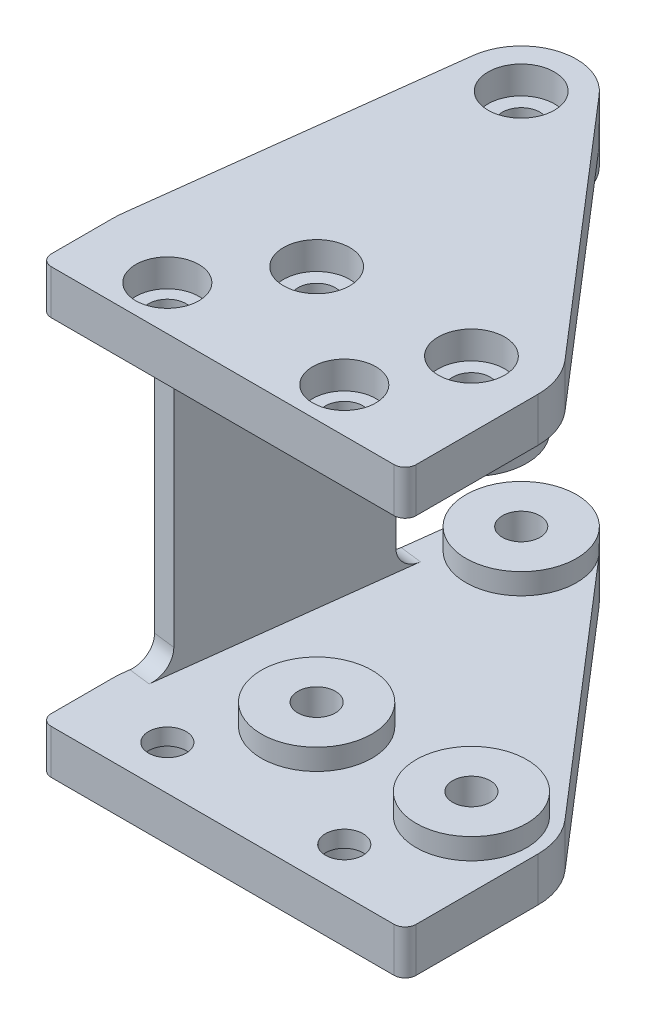
SolidWorks part; units mm, degrees
material "6061 合金"
ref_plane "前视基准面" through (0, 0, 0) normal (0, 0, 1) x (1, 0, 0)
ref_plane "上视基准面" through (0, 0, 0) normal (0, 1, 0) x (1, 0, 0)
ref_plane "右视基准面" through (0, 0, 0) normal (1, 0, 0) x (0, 0, -1)
other "Configuration Table"
sketch "草图1" plane through (0, 0, 0) normal (0, 1, 0) x (1, 0, 0)
  line L0 (0, 48.1766) -> (0, -11.3107) construction
  line L1 (-28.6592, 0) -> (28.3272, 0) construction
  line L2 (-15.5, -4) -> (15.5, -4)
  line L6 (-15.5, -4) -> (-15.5, 3)
  line L10 (-11.9622, 31.6135) -> (-15.5, 3)
  line L11 (-3.2123, 34.264) -> (16.0452, 11.9168)
  line L12 (15.5, -4) -> (17.5, -4)
  line L13 (17.5, -4) -> (17.5, 8)
  circle A0 centre (-8, 0) radius 1.7
  circle A1 centre (8, 0) radius 1.7
  arc A2 (-3.2123, 34.264) -> (-11.9622, 31.6135) centre (-7, 31) ccw
  circle A6 centre (-7, 31) radius 1.7
  arc A11 (17.5, 8) -> (16.0452, 11.9168) centre (11.5, 8) ccw
  circle A12 centre (11.5, 8) radius 1.7
  circle A13 centre (-2.5, 8) radius 1.7
  point P14 (0, -4)
  dimension "D1" = 3.4
  dimension "D3" = 4
  dimension "D6" = 10
  dimension "D7" = 2
  dimension "D8" = 3.4
  dimension "D9" = 8
  dimension "D10" = 6
  dimension "D11" = 3.4
  dimension "D12" = 3.4
  dimension "D13" = 14
  dimension "D15" = 4.5
  dimension "D14" = 23
  dimension "D2" = 8
  dimension "D4" = 31
  dimension "D5" = 7
extrude "凸台-拉伸1" add sketch "草图1" along normal blind 4 contours L11 A2 L10 L6 L2 A1 A0 region at (-0.6549, 0, -12.0055)
sketch "草图2" plane through (0, 0, 0) normal (0, -1, 0) x (1, 0, 0)
  circle A1 centre (11.5, -8) radius 5
  circle A2 centre (-2.5, -8) radius 5
  circle A3 centre (-7, -31) radius 5
  circle A7 centre (-7, -31) radius 1.7 construction
  circle A11 centre (-7, -31) radius 1.7
  circle A13 centre (-2.5, -8) radius 1.7 construction
  circle A14 centre (-2.5, -8) radius 1.7
  circle A15 centre (11.5, -8) radius 1.7 construction
  circle A16 centre (11.5, -8) radius 1.7
  dimension "D1" = 10
  dimension "D2" = 10
  dimension "D3" = 10
extrude "凸台-拉伸2" add sketch "草图2" along normal blind 1.9
sketch "草图3" plane through (0, 0, 0) normal (0, -1, 0) x (1, 0, 0)
  line L5 (-14.0853, -14.9165) -> (-4.3341, -13.7108) construction
  line L11 (-11.9622, -31.6135) -> (-15.5, -3) construction
  line L12 (-15.1319, -5.9773) -> (-12.9232, -23.8413)
  line L13 (-12.9232, -23.8413) -> (-10.9383, -23.5959)
  line L14 (-10.9383, -23.5959) -> (-13.147, -5.7319)
  line L15 (-13.147, -5.7319) -> (-15.1319, -5.9773)
  dimension "D1" = 2
  dimension "D2" = 18
  dimension "D3" = 12
extrude "凸台-拉伸3" add sketch "草图3" along normal blind 16
fillet "圆角1" radius 1 2 edges at (-15.5, 2, 4) (17.5, 2, 4)
fillet "圆角2" radius 10 1 edges at (-15.5, 2, -3)
sketch "草图5" plane through (0, 4, 0) normal (0, 1, 0) x (1, 0, 0)
  circle A0 centre (-7, 31) radius 3
  circle A1 centre (-2.5, 8) radius 3
  circle A2 centre (-8, 0) radius 2.85
  circle A3 centre (8, 0) radius 2.85
  circle A4 centre (11.5, 8) radius 3
  circle A5 centre (-2.5, 8) radius 1.7 construction
  circle A6 centre (11.5, 8) radius 1.7 construction
  dimension "D1" = 6
  dimension "D2" = 6
  dimension "D3" = 5.7
  dimension "D4" = 5.7
  dimension "D5" = 6
extrude "切除-拉伸1" cut sketch "草图5" against normal blind 2.5
mirror "镜向1" about plane through (0, -16, 0) normal (0, -1, 0) of bodies 109
fillet "圆角3" radius 2 4 edges at (-14.1394, 0, -5.8546) (-14.1394, -32, -5.8546) (-11.9307, 0, -23.7186) (-11.9307, -32, -23.7186)
